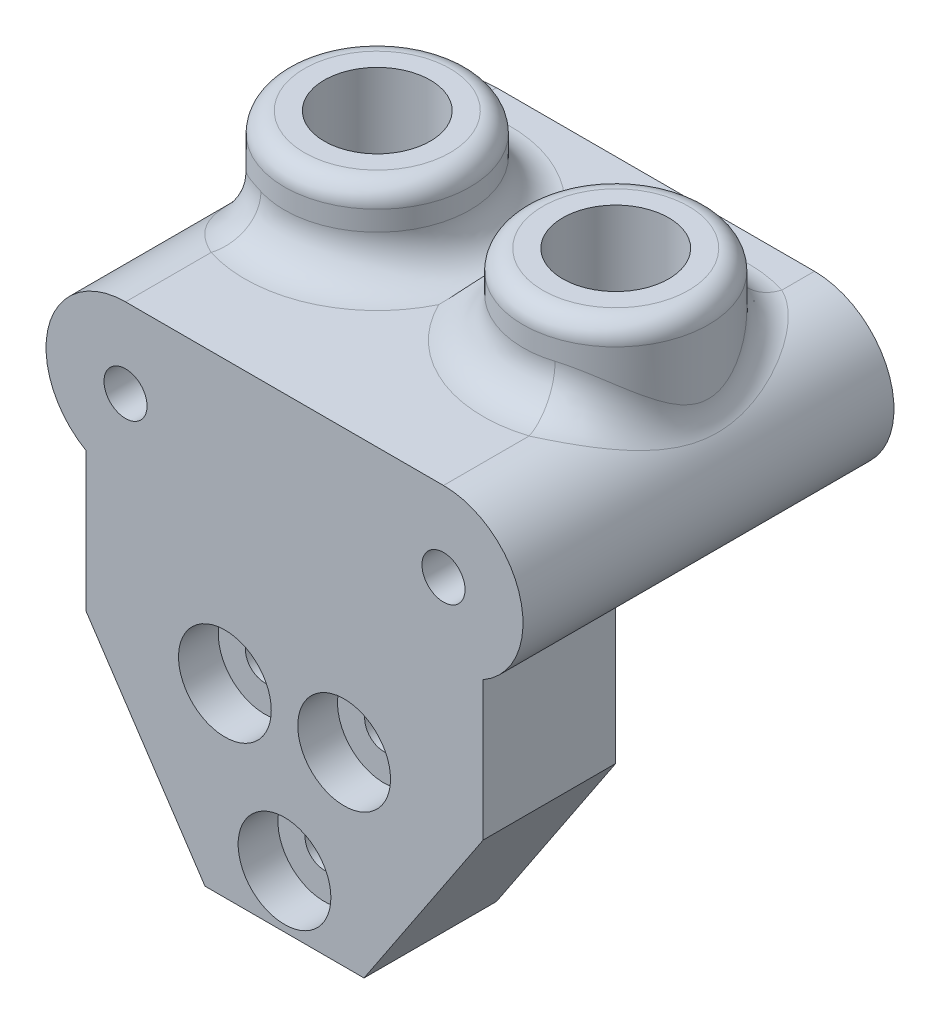
SolidWorks part; units mm, degrees
ref_plane "Front Plane" through (0, 0, 0) normal (0, 0, 1) x (1, 0, 0)
ref_plane "Top Plane" through (0, 0, 0) normal (0, 1, 0) x (1, 0, 0)
ref_plane "Right Plane" through (0, 0, 0) normal (1, 0, 0) x (0, 0, -1)
sketch "Sketch1" plane through (0, 0, 0) normal (0, 0, 1) x (1, 0, 0)
  line L0 (-288.8835, -11.9144) -> (-279.8835, -25.4352)
  line L1 (-285.8835, 9.761) -> (-261.8835, 9.761)
  line L2 (-288.8835, -1.4352) -> (-288.8835, -11.9144)
  line L3 (-279.8835, -25.4352) -> (-267.8835, -25.4352)
  line L4 (-258.8835, -1.4352) -> (-258.8835, -11.9144)
  line L5 (-258.8835, -11.9144) -> (-267.8835, -25.4352)
  circle A0 centre (-261.8835, 3.761) radius 1.625
  circle A1 centre (-285.8835, 3.761) radius 1.625
  circle A2 centre (-278.3835, -11.4352) radius 1.45
  circle A3 centre (-269.3835, -11.4352) radius 1.45
  circle A4 centre (-273.8835, -21.4352) radius 1.45
  arc A5 (-258.8835, -1.4352) -> (-261.8835, 9.761) centre (-261.8835, 3.761) ccw
  arc A6 (-285.8835, 9.761) -> (-288.8835, -1.4352) centre (-285.8835, 3.761) ccw
  point P19 (-273.8835, 9.761)
  point P21 (-273.8835, -25.4352)
  dimension "D1" = 24
  dimension "D6" = 3.25
  dimension "D9" = 2.9
  dimension "D3" = 6
  dimension "D4" = 30
  dimension "D2" = 24
  dimension "D7" = 4
  dimension "D8" = 12
  dimension "D10" = 9
  dimension "D11" = 10
  dimension "D12" = 4.5
  dimension "D14" = 15
extrude "Boss-Extrude1" add sketch "Sketch1" along normal blind 10
sketch "Sketch5" plane through (0, 0, 0) normal (0, 0, -1) x (-1, 0, 0)
  line L0 (258.8835, -1.4352) -> (288.8835, -1.4352)
  line L1 (261.8835, 9.761) -> (285.8835, 9.761)
  arc A0 (261.8835, 9.761) -> (258.8835, -1.4352) centre (261.8835, 3.761) ccw
  arc A1 (288.8835, -1.4352) -> (285.8835, 9.761) centre (285.8835, 3.761) ccw
  circle A2 centre (285.8835, 3.761) radius 1.625
  circle A4 centre (261.8835, 3.761) radius 1.625
extrude "Boss-Extrude2" add sketch "Sketch5" along normal blind 18
sketch "Sketch9" plane through (0, 9.761, 0) normal (0, 1, 0) x (1, 0, 0)
  line L0 (-261.8835, -10) -> (-285.8835, -10) construction
  circle A0 centre (-282.8835, 6) radius 7
  circle A1 centre (-264.8835, 6) radius 7
  point P6 (-273.8835, -10)
  dimension "D1" = 18
  dimension "D4" = 14
  dimension "D2" = 9
  dimension "D3" = 16
extrude "Boss-Extrude3" add sketch "Sketch9" against normal blind 8 from offset 6
sketch "Sketch4" plane through (0, 0, 10) normal (0, 0, 1) x (1, 0, 0)
  circle A0 centre (-269.3835, -11.4352) radius 3.5
  circle A1 centre (-273.8835, -21.4352) radius 3.5
  circle A2 centre (-278.3835, -11.4352) radius 3.5
  dimension "D1" = 7
extrude "Cut-Extrude2" cut sketch "Sketch4" against normal blind 3
sketch "Sketch6" plane through (0, 15.761, 0) normal (0, 1, 0) x (1, 0, 0)
  circle A0 centre (-282.8835, 6) radius 2.2
  circle A1 centre (-264.8835, 6) radius 2.2
  dimension "D1" = 4.4
sketch "Sketch7" plane through (0, 0, -18) normal (0, 0, -1) x (-1, 0, 0)
  circle A0 centre (261.8835, 3.761) radius 3.25
  circle A1 centre (285.8835, 3.761) radius 3.25
extrude "Cut-Extrude4" cut sketch "Sketch7" against normal blind 20
extrude "Cut-Extrude5" cut sketch "Sketch6" against normal blind 20
sketch "Sketch10" plane through (0, 15.761, 0) normal (0, 1, 0) x (1, 0, 0)
  circle A0 centre (-282.8835, 6) radius 4
  circle A1 centre (-264.8835, 6) radius 4
  dimension "D1" = 8
extrude "Cut-Extrude6" cut sketch "Sketch10" against normal blind 6
fillet "Fillet1" radius 3 4 edges at (-257.8841, 8.2337, -5.9073) (-289.8829, 8.2337, -6.0927) (-271.8835, 9.761, -6) (-275.8835, 9.761, -6)
fillet "Fillet2" radius 1.5 2 edges at (-282.8835, 15.761, 1) (-264.8835, 15.761, 1)
